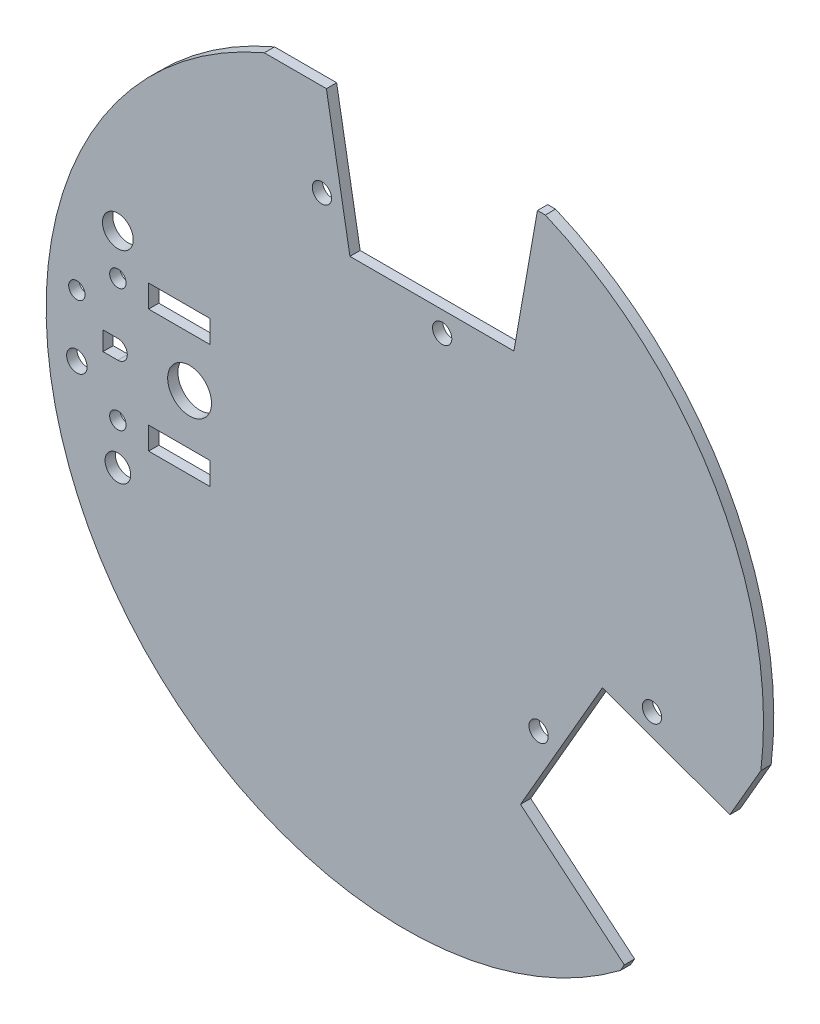
SolidWorks part; units mm, degrees
material "Balsa"
ref_plane "Plan de face" through (0, 0, 0) normal (0, 0, 1) x (1, 0, 0)
ref_plane "Plan de dessus" through (0, 0, 0) normal (0, 1, 0) x (1, 0, 0)
ref_plane "Plan de droite" through (0, 0, 0) normal (1, 0, 0) x (0, 0, -1)
sketch "Esquisse1" plane through (0, 0, 0) normal (0, 0, 1) x (1, 0, 0)
  circle A0 centre (0, 0) radius 175
extrude "Boss.-Extru.1" add sketch "Esquisse1" along normal blind 5
sketch "Esquisse2" plane through (0, 0, 0) normal (0, 0, -1) x (-1, 0, 0)
  line L1 (-13.2204, 90.8876) -> (-13.2204, 0) construction
  line L3 (0, 0) -> (-290.6498, 0) construction
  line L5 (26.7796, 95.8876) -> (38.2633, 161.0152)
  line L6 (38.2633, 161.0152) -> (68.5501, 161.0152)
  line L7 (68.5501, 161.0152) -> (68.5501, 190.2461)
  line L8 (-53.2204, 95.8876) -> (-64.7042, 161.0152)
  line L9 (-64.7042, 161.0152) -> (-94.991, 161.0152)
  line L10 (-94.991, 161.0152) -> (-94.991, 190.2461)
  line L11 (-94.991, 190.2461) -> (68.5501, 190.2461)
  line L12 (26.7796, 95.8876) -> (-53.2204, 95.8876)
  line L13 (-96.4309, -24.752) -> (-158.5749, -47.3706)
  line L14 (-158.5749, -47.3706) -> (-173.7183, -21.1414)
  line L15 (-173.7183, -21.1414) -> (-199.033, -35.7569)
  line L16 (-56.4309, -94.034) -> (-107.0911, -136.543)
  line L17 (-107.0911, -136.543) -> (-91.9477, -162.7722)
  line L18 (-91.9477, -162.7722) -> (-117.2625, -177.3877)
  line L19 (-117.2625, -177.3877) -> (-199.033, -35.7569)
  line L20 (-96.4309, -24.752) -> (-56.4309, -94.034)
  line L21 (-72.1008, -56.893) -> (6.6102, -11.4492) construction
  line L22 (0, 0) -> (87.5, -151.5544) construction
  circle A0 centre (-18.2204, 85.8876) radius 4.7
  circle A1 centre (40.4604, 115.8876) radius 4.7
  circle A2 centre (-65.2706, -58.7232) radius 4.7
  circle A3 centre (-120.5918, -22.9041) radius 4.7
  circle A4 centre (0, 0) radius 175 construction
  point P43 (0, 0)
  dimension "D5" = 9.4
  dimension "D6" = 9.4
  dimension "D1" = 2
  dimension "D2" = 95.8876
  dimension "D3" = 13.2204
  dimension "D4" = 100
  dimension "D7" = 80
  dimension "D8" = 65.1275
extrude "Enlèv. mat.-Extru.1" cut sketch "Esquisse2" against normal blind 5
sketch "Leds, bout., tirette" plane through (0, 0, 5) normal (0, 0, 1) x (1, 0, 0)
  line L0 (0, 0) -> (0, 203.1142) construction
  line L1 (0, 0) -> (-214.6297, 0) construction
  line L2 (-156.4682, 78.3754) -> (-90, 40) construction
  line L3 (-90, 40) -> (-90, -40) construction
  line L4 (-90, -40) -> (-156.4682, -78.3754) construction
  line L5 (-140, 0) -> (-89.4612, 0) construction
  line L6 (-140, -4.6) -> (-147.25, -4.6)
  line L7 (-140, 4.6) -> (-147.25, 4.6)
  line L8 (-147.25, 4.6) -> (-147.25, -4.6)
  line L9 (-125, 35.5) -> (-95, 35.5)
  line L10 (-125, 35.5) -> (-125, 24.5)
  line L11 (-95, 35.5) -> (-95, 24.5)
  line L12 (-125, 24.5) -> (-95, 24.5)
  line L13 (-125, -24.5) -> (-95, -24.5)
  line L14 (-125, -24.5) -> (-125, -35.5)
  line L15 (-95, -24.5) -> (-95, -35.5)
  line L16 (-125, -35.5) -> (-95, -35.5)
  line L17 (-95, -30) -> (-140, -30) construction
  line L18 (-95, 30) -> (-140, 30) construction
  line L19 (-140, 4.6) -> (-140, -4.6) construction
  arc A0 (-68.5501, 161.0152) -> (105.1682, -139.8737) centre (0, 0) ccw construction
  arc A1 (-156.4682, 78.3754) -> (-156.4682, -78.3754) centre (0, 0) ccw construction
  circle A2 centre (-105, 0) radius 10.7
  circle A3 centre (-140, -50) radius 6.25
  circle A4 centre (-140, 30) radius 4
  circle A5 centre (-140, -30) radius 4
  circle A6 centre (-160, 15) radius 4
  circle A7 centre (-160, -15) radius 5
  arc A8 (-140, -4.6) -> (-140, 4.6) centre (-140, 0) ccw
  circle A9 centre (-140, 50) radius 7.5
  point P26 (-13.0506, -157.1537)
  dimension "D2" = 90
  dimension "D5" = 12.5
  dimension "D6" = 21.4
  dimension "D7" = 8
  dimension "D8" = 10
  dimension "D9" = 4.6
  dimension "D12" = 15
  dimension "D1" = 90
  dimension "D3" = 80
  dimension "D4" = 120
  dimension "D10" = 9.2
  dimension "D11" = 7.25
  dimension "D13" = 11
  dimension "D14" = 30
  dimension "D15" = 5
  dimension "D16" = 30
  dimension "D17" = 45
  dimension "D18" = 15
  dimension "D19" = 35
  dimension "D20" = 70
  dimension "D21" = 15
  dimension "D22" = 50
  dimension "D23" = 50
extrude "Leds, buttons" cut sketch "Leds, bout., tirette" against normal blind 10
